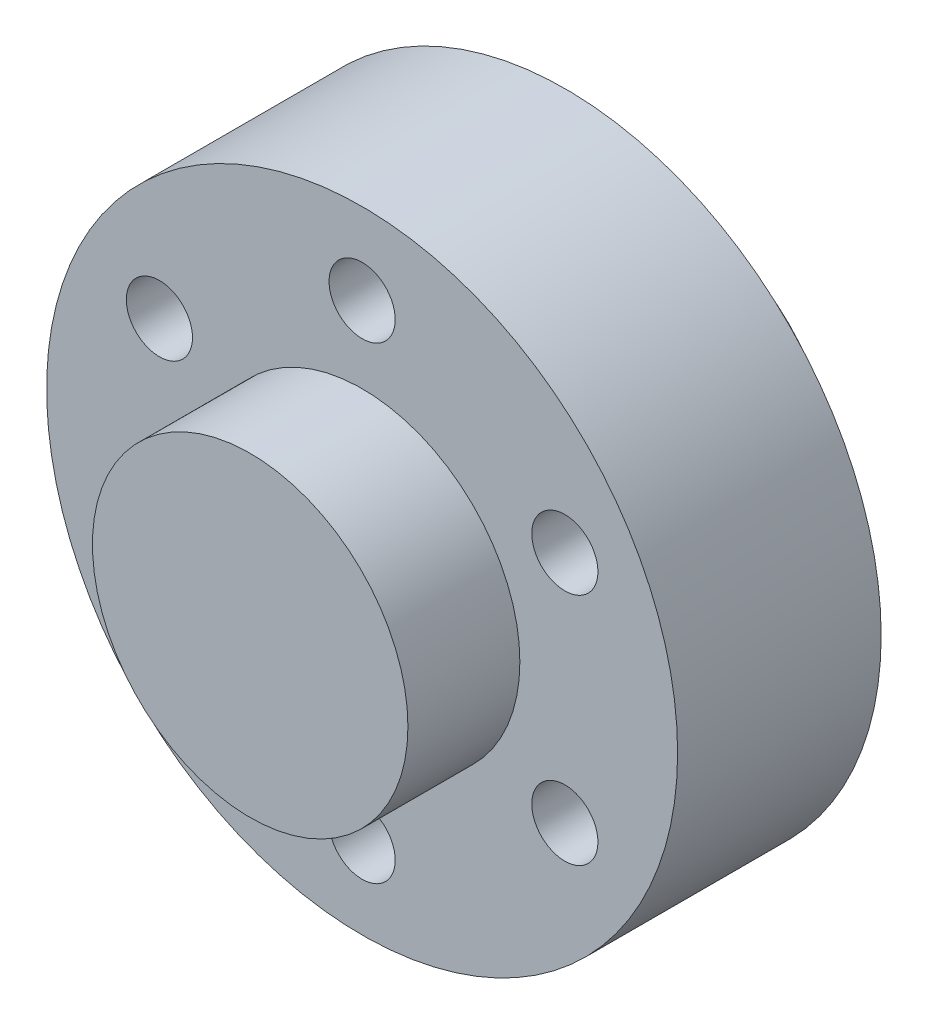
SolidWorks part; units mm, degrees
ref_plane "Front Plane" through (0, 0, 0) normal (0, 0, 1) x (1, 0, 0)
ref_plane "Top Plane" through (0, 0, 0) normal (0, 1, 0) x (1, 0, 0)
ref_plane "Right Plane" through (0, 0, 0) normal (1, 0, 0) x (0, 0, -1)
sketch "Sketch2" plane through (0, 0, 0) normal (0, 0, 1) x (1, 0, 0)
  line L0 (0, 20.3178) -> (0, -21.083) construction
  circle A0 centre (0, 0) radius 9.5
  circle A1 centre (0, 0) radius 11.5 construction
  circle A3 centre (0, 0) radius 15.5
  circle A4 centre (0, 11.5) radius 1.625
  circle A10 centre (9.9593, 5.75) radius 1.625
  circle A11 centre (9.9593, -5.75) radius 1.625
  circle A12 centre (0, -11.5) radius 1.625
  circle A13 centre (-9.9593, -5.75) radius 1.625
  circle A14 centre (-9.9593, 5.75) radius 1.625
  point P21 (1.7321, -1)
  point P22 (0.866, -0.5)
  point P23 (0, 0)
  dimension "D1" = 19
  dimension "D2" = 6
  dimension "D3" = 23
  dimension "D4" = 31
  dimension "D5" = 3.25
extrude "Boss-Extrude1" add sketch "Sketch2" along normal blind 10 contours A3 A14 A13 A12 A11 A10 A4 A0 | A0 region at (0, 0, 0) region at (-15.0616, 0, 0)
sketch "Sketch3" plane through (0, 0, 10) normal (0, 0, 1) x (1, 0, 0)
  circle A0 centre (0, 0) radius 7.75
  dimension "D1" = 15.5
extrude "Boss-Extrude2" add sketch "Sketch3" along normal blind 5.5
sketch "Sketch6" plane through (0, 0, 0) normal (0, 0, -1) x (-1, 0, 0)
  circle A0 centre (0, 0) radius 7.75
  dimension "D1" = 15.5
extrude "Boss-Extrude4" add sketch "Sketch6" along normal blind 5.5 contours A0
sketch "Sketch7" plane through (0, 0, -5.5) normal (0, 0, -1) x (-1, 0, 0)
  circle A0 centre (0, 0) radius 2
  dimension "D1" = 4
extrude "Boss-Extrude5" add sketch "Sketch7" along normal blind 1
fillet "Fillet2" radius 0.05 1 edges at (-2, 0, -6.5)
sketch "Sketch9" plane through (0, 0, -6.5) normal (0, 0, -1) x (-1, 0, 0)
  line L1 (-1.2247, 1.25) -> (1.2247, 1.25)
  arc A0 (-1.2247, 1.25) -> (1.2247, 1.25) centre (0, 0) ccw
  circle A1 centre (0, -0.25) radius 1.5 construction
  dimension "D1" = 3.5
  dimension "D2" = 3
extrude "Cut-Extrude1" cut sketch "Sketch9" against normal blind 11
